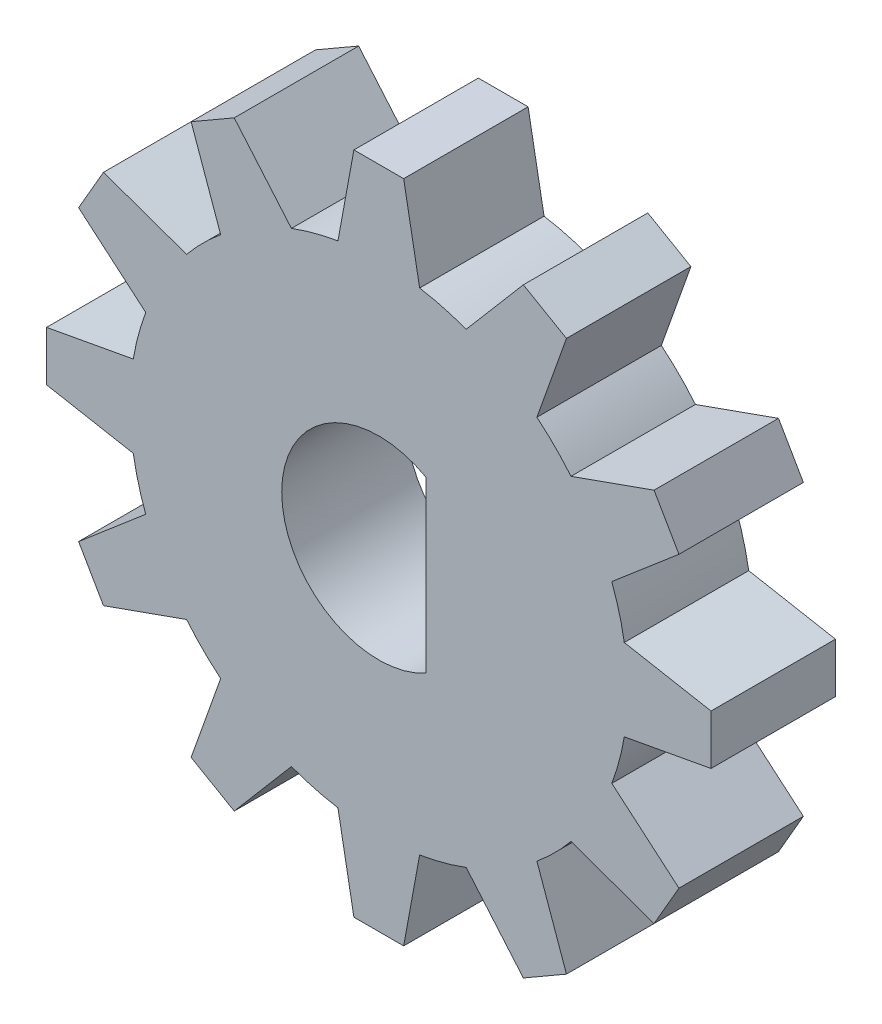
SolidWorks part; units mm, degrees
ref_plane "Front Plane" through (0, 0, 0) normal (0, 0, 1) x (1, 0, 0)
ref_plane "Top Plane" through (0, 0, 0) normal (0, 1, 0) x (1, 0, 0)
ref_plane "Right Plane" through (0, 0, 0) normal (1, 0, 0) x (0, 0, -1)
sketch "Sketch1" plane through (0, 0, 0) normal (0, 0, 1) x (1, 0, 0)
  circle A0 centre (0, 0) radius 10
  dimension "D1" = 20
extrude "Boss-Extrude1" add sketch "Sketch1" along normal blind 5
sketch "Sketch3" plane through (0, 0, 0) normal (0, 0, 1) x (1, 0, 0)
  line L0 (0, -13.35) -> (0, 13.35) construction
  line L1 (-1, 13.35) -> (1, 13.35)
  line L2 (-1, 13.35) -> (-1.8, 9)
  line L3 (-1.8, 9) -> (1.8, 9)
  line L4 (1.8, 9) -> (1, 13.35)
  point P3 (0, 0)
  point P4 (0, 9)
  point P6 (0, 13.35)
  dimension "D1" = 13.35
  dimension "D2" = 3.6
  dimension "D3" = 2
  dimension "D4" = 9
extrude "Boss-Extrude2" add sketch "Sketch3" along normal blind 5
ref_axis "Axis2" through (0, 0, 5) along (0, 0, -1)
pattern_circular "CirPattern1" count 12 every 30 about axis through (0, 0, 0) along (0, 0, 1) of "Boss-Extrude2"
sketch "Sketch4" plane through (0, 0, 0) normal (0, 0, 1) x (1, 0, 0)
  line L0 (1.9, 3.4059) -> (1.9, -3.4059)
  arc A0 (1.9, 3.4059) -> (1.9, -3.4059) centre (0, 0) ccw
  dimension "D1" = 7.8
  dimension "D2" = 1.9
extrude "Cut-Extrude1" cut sketch "Sketch4" along normal blind 7
